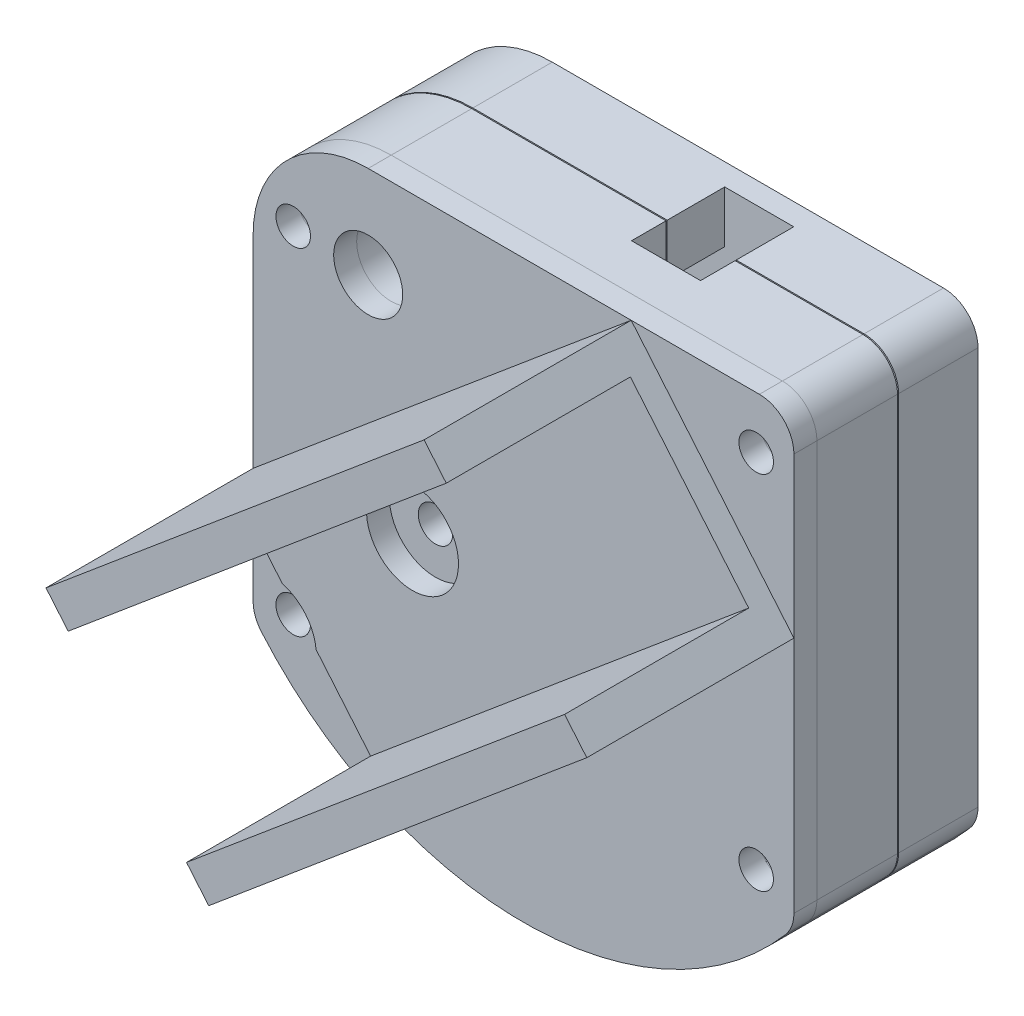
SolidWorks part; units mm, degrees
ref_plane "Front Plane" through (0, 0, 0) normal (0, 0, 1) x (1, 0, 0)
ref_plane "Top Plane" through (0, 0, 0) normal (0, 1, 0) x (1, 0, 0)
ref_plane "Right Plane" through (0, 0, 0) normal (1, 0, 0) x (0, 0, -1)
sketch "Sketch1" plane through (0, 0, 0) normal (0, 0, 1) x (1, 0, 0)
  line L0 (-11.1125, 0) -> (11.1125, 0) construction
  line L1 (17.1125, 10) -> (-29.8875, 10)
  line L2 (17.1125, 10) -> (17.1125, -40)
  line L3 (17.1125, -40) -> (-29.8875, -40)
  line L4 (-29.8875, 10) -> (-29.8875, -40)
  line L5 (11.1125, 0) -> (11.1125, -18) construction
  dimension "D1" = 10
  dimension "D2" = 47
  dimension "D3" = 6
  dimension "D4" = 50
extrude "Boss-Extrude1" add sketch "Sketch1" along normal blind 4 and the other way blind 10
sketch "Sketch2" plane through (0, -40, 0) normal (0, -1, 0) x (1, 0, 0)
  line L0 (-29.8875, -10) -> (-29.8875, 4) construction
  circle A0 centre (-19.8875, -3) radius 3.25
  point P4 (0, 0)
  point P5 (-29.8875, -3)
  dimension "D1" = 6.5
  dimension "D2" = 10
extrude "Cut-Extrude1" cut sketch "Sketch2" against normal blind 34
sketch "Sketch3" plane through (0, 0, 4) normal (0, 0, 1) x (1, 0, 0)
  line L0 (-29.8875, 10) -> (-29.8875, -40) construction
  line L1 (17.1125, -40) -> (17.1125, 10) construction
  line L5 (-29.8875, -40) -> (17.1125, -40) construction
  line L6 (-29.8875, -28.6481) -> (-29.8875, -40)
  line L7 (-29.8875, -40) -> (17.1125, -40)
  line L8 (17.1125, -40) -> (17.1125, -28.6481)
  arc A0 (-29.8875, -28.6481) -> (17.1125, -28.6481) centre (-6.3875, -10) ccw
  line M2 (17.1125, -40) -> (17.1125, 10)
  line M4 (-29.8875, 10) -> (-29.8875, -40)
  line M5 (-29.8875, -40) -> (17.1125, -40)
  dimension "D1" = 30
extrude "Cut-Extrude2" cut sketch "Sketch3" against normal blind 34 contours A0 M4 M5 | A0 L7 M2
fillet "Fillet6" radius 3 2 edges at (-29.8875, -28.6481, -3) (17.1125, -28.6481, -3)
sketch "Sketch5" plane through (0, 0, 0) normal (0, 1, 0) x (1, 0, 0)
  line L0 (-11.1125, 0) -> (11.1125, 0) construction
  line L1 (-42.8973, 0) -> (36.217, 0)
  line L2 (-42.8973, 0) -> (-42.8973, 0.1)
  line L3 (-42.8973, 0.1) -> (36.217, 0.1)
  line L4 (36.217, 0) -> (36.217, 0.1)
  dimension "D1" = 0.1
extrude "Cut-Extrude3" cut sketch "Sketch5" against normal through all both and the other way through all
sketch "Sketch6" plane through (0, 0, 0) normal (0, 0, -1) x (-1, 0, 0)
  line L0 (-9.75, -19.3625) -> (-9.75, -21.1375) construction
  line L1 (9.75, -21.1375) -> (9.75, -19.3625) construction
  line L2 (-11.1125, 0) -> (-11.1125, -18) construction
  line L4 (-11.6125, 10) -> (-11.6125, -18.3543)
  line L6 (11.6125, 10) -> (11.6125, -18.3543)
  line L7 (11.1125, -85.0724) -> (11.1125, -22.5) construction
  line L8 (29.8875, 10) -> (-17.1125, 10) construction
  line L9 (-11.6125, 10) -> (-17.1125, 10)
  line L10 (11.6125, -22.1457) -> (11.6125, -39.5415)
  line L11 (-11.6125, -22.1457) -> (-11.6125, -34)
  line L12 (-11.6125, 0.5) -> (-7.4, 0.5)
  line L13 (-3, 5.5) -> (-3, 10)
  line L14 (3, 10) -> (3, 5.5)
  line L15 (-17.1125, 10) -> (-17.1125, -27.5713)
  line L16 (18.6375, -37.385) -> (18.6375, -6)
  line L17 (18.6375, -6) -> (21.1375, -6)
  line L18 (21.1375, -6) -> (21.1375, -36.1235)
  line L19 (29.8875, -27.5713) -> (29.8875, 10)
  line L20 (29.8875, 10) -> (-17.1125, 10)
  line L21 (-17.1125, 10) -> (-17.1125, -27.5713)
  line L22 (18.6375, -37.385) -> (18.6375, -6)
  line L23 (18.6375, -6) -> (21.1375, -6)
  line L24 (21.1375, -6) -> (21.1375, -36.1235)
  line L25 (29.8875, -27.5713) -> (29.8875, 10)
  line L26 (29.8875, 10) -> (11.6125, 10)
  line L27 (3, 5.5) -> (7.4, 5.5)
  line L28 (3, 10) -> (11.6125, 10)
  line L29 (-11.6125, 10) -> (-3, 10)
  line L30 (-7.4, 0.5) -> (-7.4, 5.5)
  line L31 (-7.4, 5.5) -> (-3, 5.5)
  line L32 (7.4, 5.5) -> (7.4, 0.5)
  line L33 (7.4, 0.5) -> (11.6125, 0.5)
  line L34 (11.1125, 0) -> (-11.1125, 0) construction
  line L35 (-5, 2.5) -> (-5, -4.5) construction
  line L36 (5, -4.5) -> (5, 2.5) construction
  arc A0 (-11.6125, -22.1457) -> (-11.6125, -18.3543) centre (-12.25, -20.25) ccw
  arc A1 (11.6125, -18.3543) -> (11.6125, -22.1457) centre (12.25, -20.25) ccw
  arc A2 (-16.3903, -29.5236) -> (18.6375, -37.385) centre (6.3875, -10) ccw construction
  arc A3 (11.6125, -39.5415) -> (18.6375, -37.385) centre (6.3875, -10) ccw
  arc A5 (-16.3903, -29.5236) -> (18.6375, -37.385) centre (6.3875, -10) ccw
  arc A6 (21.1375, -36.1235) -> (29.1653, -29.5236) centre (6.3875, -10) ccw
  arc A7 (-16.3903, -29.5236) -> (-11.6125, -34) centre (6.3875, -10) ccw
  arc A8 (21.1375, -36.1235) -> (29.1653, -29.5236) centre (6.3875, -10) ccw
  arc A12 (-17.1125, -27.5713) -> (-16.3903, -29.5236) centre (-14.1125, -27.5713) ccw
  arc A13 (-17.1125, -27.5713) -> (-16.3903, -29.5236) centre (-14.1125, -27.5713) ccw
  arc A14 (29.1653, -29.5236) -> (29.8875, -27.5713) centre (26.8875, -27.5713) ccw
  arc A15 (29.1653, -29.5236) -> (29.8875, -27.5713) centre (26.8875, -27.5713) ccw
  point P11 (-9.75, -20.25)
  point P15 (9.75, -20.25)
  point P49 (0, 0)
  point P50 (0, 0)
  point P51 (0, 0)
  line M11 (-17.1125, 10) -> (-17.1125, -27.5713)
  arc M12 (-16.3903, -29.5236) -> (18.6375, -37.385) centre (6.3875, -10) ccw
  line M13 (18.6375, -37.385) -> (18.6375, -6)
  line M14 (18.6375, -6) -> (21.1375, -6)
  line M15 (21.1375, -6) -> (21.1375, -36.1235)
  arc M16 (21.1375, -36.1235) -> (29.1653, -29.5236) centre (6.3875, -10) ccw
  line M17 (29.8875, -27.5713) -> (29.8875, 10)
  line M18 (29.8875, 10) -> (-17.1125, 10)
  dimension "D1" = 4
  dimension "D2" = 4
  dimension "D3" = 2.5
  dimension "D4" = 2.5
  dimension "D5" = 0.5
  dimension "D6" = 0.5
  dimension "D8" = 0.5
  dimension "D9" = 2.4
  dimension "D10" = 5
  dimension "D11" = 2.4
  dimension "D12" = 6
  dimension "D7" = 0
extrude "Boss-Extrude2" add sketch "Sketch6" along normal blind 3 contours L30 L31 L13 L4 L12 M18 | L11 A0 L4 M18 M11 M12 | L6 A1 L10 M12 M13 M14 M15 M16 M17 M18 | L32 L33 L6 L14 L27 M18
sketch "Sketch7" plane through (0, -6, 0) normal (0, -1, 0) x (1, 0, 0)
  circle A0 centre (-19.8951, -2.9003) radius 3.35
extrude "Cut-Extrude4" cut sketch "Sketch7" along normal through all
sketch "Sketch8" plane through (0, 10, 0) normal (0, 1, 0) x (1, 0, 0)
  line L0 (3, 3) -> (17.1125, 3) construction
  line L1 (17.1125, 3.1) -> (-29.8875, 3.1)
  line L2 (17.1125, 3.1) -> (17.1125, 0.1)
  line L3 (17.1125, 0.1) -> (-29.8875, 0.1)
  line L4 (-29.8875, 3.1) -> (-29.8875, 0.1)
  line L5 (17.1125, 3) -> (17.1125, -4) construction
  line L6 (-29.8875, 3) -> (-29.8875, -4) construction
  line L7 (17.1125, 0.1) -> (-29.8875, 0.1) construction
  point P6 (17.1125, -2.831)
  point P9 (-29.8875, -2.831)
  point P12 (-29.8875, 0)
  point P13 (17.1125, 0)
  dimension "D1" = 0.1
extrude "Cut-Extrude5" cut sketch "Sketch8" against normal through all both and the other way through all
chamfer "Chamfer1" distance 4 angle 70 1 edges at (-19.8875, -6, -3.1)
sketch "Sketch9" plane through (0, -6, 0) normal (0, -1, 0) x (1, 0, 0)
  line L1 (-23.2437, -3) -> (-16.5466, -3)
  line L3 (-23.2437, -3) -> (-16.5466, -3)
  arc A1 (-16.5466, -3) -> (-23.2437, -3) centre (-19.8951, -2.9003) ccw
  arc A3 (-16.5466, -3) -> (-23.2437, -3) centre (-19.8951, -2.9003) ccw
  dimension "D1" = 0
extrude "Cut-Extrude6" cut sketch "Sketch9" against normal up to vertex (11.2647 mm away)
sketch "Sketch11" plane through (0, 0.5, 0) normal (0, -1, 0) x (1, 0, 0)
  line L0 (16.3903, -3.1) -> (-16.639, -3.1) construction
  line L1 (-10.6125, -3.1) -> (10.6125, -3.1)
  line L2 (-10.6125, -3.1) -> (-10.6125, -1.2)
  line L3 (-10.6125, -1.2) -> (10.6125, -1.2)
  line L4 (10.6125, -3.1) -> (10.6125, -1.2)
  line L5 (11.6125, -3) -> (11.6125, 0) construction
  line L6 (-11.6125, -3) -> (-11.6125, 0) construction
  line L7 (0, -0.9) -> (-10.1826, -0.9) construction
  dimension "D1" = 1
  dimension "D2" = 1
  dimension "D3" = 0.3
extrude "Boss-Extrude3" add sketch "Sketch11" along normal up to surface (15.201 mm away) from offset 25
sketch "Sketch12" plane through (0, 0, -3.1) normal (0, 0, 1) x (1, 0, 0)
  line L0 (-11.6125, -8) -> (11.6125, -8)
  line L1 (-3, 10) -> (3, 10)
  line L8 (7.4, 5.5) -> (7.4, 0.5)
  line L9 (3, 5.5) -> (7.4, 5.5)
  line L10 (3, 10) -> (3, 5.5)
  line L11 (17.1125, 10) -> (3, 10)
  line L12 (17.1125, -27.5713) -> (17.1125, 10)
  line L13 (11.6125, -22.1457) -> (11.6125, -34)
  line L14 (11.6125, 0.5) -> (11.6125, -18.3543)
  line L15 (7.4, 0.5) -> (11.6125, 0.5)
  line L16 (7.4, 5.5) -> (7.4, 0.5)
  line L17 (3, 5.5) -> (7.4, 5.5)
  line L18 (3, 10) -> (3, 5.5)
  line L19 (17.1125, 10) -> (3, 10)
  line L21 (11.6125, -22.1457) -> (11.6125, -34)
  line L22 (11.6125, 0.5) -> (11.6125, -18.3543)
  line L23 (7.4, 0.5) -> (11.6125, 0.5)
  line L27 (-23.2437, 4.9899) -> (-16.5466, 4.9899)
  line L28 (-23.2437, -34.8167) -> (-23.2437, 4.9899)
  line L29 (-29.8875, 10) -> (-29.8875, -27.5713)
  line L30 (-3, 10) -> (-29.8875, 10)
  line L31 (-3, 5.5) -> (-3, 10)
  line L32 (-7.4, 5.5) -> (-3, 5.5)
  line L33 (-7.4, 0.5) -> (-7.4, 5.5)
  line L34 (-11.6125, 0.5) -> (-7.4, 0.5)
  line L35 (-11.6125, -18.3543) -> (-11.6125, 0.5)
  line L36 (-11.6125, -39.5415) -> (-11.6125, -22.1457)
  line L37 (-16.5466, 4.9899) -> (-16.5466, -38.2275)
  line L42 (-3, 5.5) -> (-3, 10)
  line L43 (-7.4, 5.5) -> (-3, 5.5)
  line L44 (-7.4, 0.5) -> (-7.4, 5.5)
  line L45 (-11.6125, 0.5) -> (-7.4, 0.5)
  line L46 (-11.6125, -18.3543) -> (-11.6125, 0.5)
  line L47 (-11.6125, -39.5415) -> (-11.6125, -22.1457)
  line L51 (-23.2437, 4.9899) -> (-16.5466, 4.9899)
  arc A2 (11.6125, -34) -> (16.3903, -29.5236) centre (-6.3875, -10) ccw
  arc A3 (11.6125, -18.3543) -> (11.6125, -22.1457) centre (12.25, -20.25) ccw
  arc A5 (11.6125, -18.3543) -> (11.6125, -22.1457) centre (12.25, -20.25) ccw
  arc A7 (-29.1653, -29.5236) -> (-23.2437, -34.8167) centre (-6.3875, -10) ccw
  arc A8 (-11.6125, -22.1457) -> (-11.6125, -18.3543) centre (-12.25, -20.25) ccw
  arc A9 (-16.5466, -38.2275) -> (-11.6125, -39.5415) centre (-6.3875, -10) ccw
  arc A11 (-11.6125, -22.1457) -> (-11.6125, -18.3543) centre (-12.25, -20.25) ccw
  arc A13 (16.3903, -29.5236) -> (17.1125, -27.5713) centre (14.1125, -27.5713) ccw
  arc A14 (16.3903, -29.5236) -> (17.1125, -27.5713) centre (14.1125, -27.5713) ccw
  arc A16 (-29.8875, -27.5713) -> (-29.1653, -29.5236) centre (-26.8875, -27.5713) ccw
  arc A17 (-29.8875, -27.5713) -> (-29.1653, -29.5236) centre (-26.8875, -27.5713) ccw
  line M32 (17.1125, 10) -> (-29.8875, 10)
  dimension "D3" = 18
  dimension "D1" = 0
  dimension "D2" = 0
extrude "Cut-Extrude8" cut sketch "Sketch12" against normal blind 5 contours L46 L0 L22 L23 L16 L17 L18 L42 L43 L44 L45 M32
sketch "Sketch13" plane through (0, 0, 4) normal (0, 0, 1) x (1, 0, 0)
  line L0 (17.1125, -6.853) -> (2.9712, 10)
  line L1 (17.1125, -6.853) -> (-15.7462, -34.4247)
  line L2 (2.9712, 10) -> (-29.8875, -17.5717)
  line L3 (-15.7462, -34.4247) -> (-29.8875, -17.5717)
  line L4 (17.1125, -27.5713) -> (17.1125, 10) construction
  line L5 (17.1125, 10) -> (-29.8875, 10) construction
  line L6 (-29.8875, 10) -> (-29.8875, -27.5713) construction
  point P6 (0, 0)
  point P7 (0, 0)
  point P8 (-41.2551, 21.0545)
  point P11 (0, 0)
  dimension "D1" = 130
  dimension "D2" = 22
extrude "Boss-Extrude4" add sketch "Sketch13" along normal blind 20 separate body
fillet "Fillet1" radius 10 1 edges at (-29.8875, 10, 0.5)
sketch "Sketch15" plane through (0, 0, 4) normal (0, 0, 1) x (1, 0, 0)
  line L14 (17.1125, 10) -> (-19.8875, 10)
  line L15 (-29.8875, 0) -> (-29.8875, -27.5713)
  line L16 (17.1125, -27.5713) -> (17.1125, 10)
  line L17 (17.1125, 10) -> (-19.8875, 10)
  line L18 (-29.8875, 0) -> (-29.8875, -27.5713)
  line L19 (17.1125, -27.5713) -> (17.1125, 10)
  arc A8 (-19.8875, 10) -> (-29.8875, 0) centre (-19.8875, 0) ccw
  arc A9 (-29.1653, -29.5236) -> (16.3903, -29.5236) centre (-6.3875, -10) ccw
  arc A10 (-19.8875, 10) -> (-29.8875, 0) centre (-19.8875, 0) ccw
  arc A11 (-29.1653, -29.5236) -> (16.3903, -29.5236) centre (-6.3875, -10) ccw
  arc A14 (-29.8875, -27.5713) -> (-29.1653, -29.5236) centre (-26.8875, -27.5713) ccw
  arc A15 (-29.8875, -27.5713) -> (-29.1653, -29.5236) centre (-26.8875, -27.5713) ccw
  arc A16 (16.3903, -29.5236) -> (17.1125, -27.5713) centre (14.1125, -27.5713) ccw
  arc A17 (16.3903, -29.5236) -> (17.1125, -27.5713) centre (14.1125, -27.5713) ccw
  dimension "D1" = 0
extrude "Boss-Extrude5" add sketch "Sketch15" along normal blind 2
sketch "Sketch16" plane through (-26.1911, -21.9769, 0) normal (-0.766, -0.6428, 0) x (0, 0, 1)
  line L0 (24, 5.7506) -> (24, -16.2494) construction
  line L1 (24, 2.7506) -> (8, 2.7506)
  line L2 (24, 2.7506) -> (24, -13.2494)
  line L3 (24, -13.2494) -> (8, -13.2494)
  line L4 (8, 2.7506) -> (8, -13.2494)
  line L6 (6, 5.7506) -> (6, -16.2494) construction
  point P6 (8, 4.8465)
  point P11 (6, -5.2494)
  point P12 (8, -5.2494)
  dimension "D1" = 16
  dimension "D2" = 16
extrude "Cut-Extrude9" cut sketch "Sketch16" against normal through all
sketch "Sketch17" plane through (0, 0, 6) normal (0, 0, 1) x (1, 0, 0)
  line L21 (-3, 5.5) -> (-3, 10)
  line L22 (-3, 10) -> (-29.8875, 10)
  line L23 (-29.8875, 10) -> (-29.8875, -27.5713)
  line L24 (-23.136, -34.8895) -> (-23.136, 4.9899)
  line L25 (-23.136, 4.9899) -> (-16.639, 4.9899)
  line L26 (-16.639, 4.9899) -> (-16.639, -38.1941)
  line L27 (-10.6125, -39.701) -> (-10.6125, -24.5)
  line L28 (-10.6125, -24.5) -> (10.6125, -24.5)
  line L29 (10.6125, -24.5) -> (10.6125, -34.7184)
  line L30 (17.1125, -27.5713) -> (17.1125, 10)
  line L31 (17.1125, 10) -> (3, 10)
  line L32 (3, 10) -> (3, 5.5)
  line L33 (3, 5.5) -> (7.4, 5.5)
  line L34 (7.4, 5.5) -> (7.4, 0.5)
  line L35 (7.4, 0.5) -> (11.6125, 0.5)
  line L36 (11.6125, 0.5) -> (11.6125, -8)
  line L37 (11.6125, -8) -> (-11.6125, -8)
  line L38 (-11.6125, -8) -> (-11.6125, 0.5)
  line L39 (-11.6125, 0.5) -> (-7.4, 0.5)
  line L40 (-7.4, 0.5) -> (-7.4, 5.5)
  line L41 (-7.4, 5.5) -> (-3, 5.5)
  line L42 (-3, 5.5) -> (-3, 10) construction
  line L43 (-3, 10) -> (-29.8875, 10) construction
  line L44 (-29.8875, 10) -> (-29.8875, -27.5713) construction
  line L45 (-23.136, -34.8895) -> (-23.136, 4.9899) construction
  line L47 (-16.639, 4.9899) -> (-16.639, -38.1941) construction
  line L48 (-10.6125, -39.701) -> (-10.6125, -24.5) construction
  line L49 (-10.6125, -24.5) -> (10.6125, -24.5) construction
  line L50 (10.6125, -24.5) -> (10.6125, -34.7184) construction
  line L51 (17.1125, -27.5713) -> (17.1125, 10) construction
  line L52 (17.1125, 10) -> (3, 10) construction
  line L53 (3, 10) -> (3, 5.5) construction
  line L54 (3, 5.5) -> (7.4, 5.5) construction
  line L55 (7.4, 5.5) -> (7.4, 0.5) construction
  line L56 (7.4, 0.5) -> (11.6125, 0.5) construction
  line L57 (11.6125, 0.5) -> (11.6125, -8) construction
  line L58 (11.6125, -8) -> (-11.6125, -8) construction
  line L59 (-11.6125, -8) -> (-11.6125, 0.5) construction
  line L60 (-11.6125, 0.5) -> (-7.4, 0.5) construction
  line L61 (-7.4, 0.5) -> (-7.4, 5.5) construction
  line L62 (-7.4, 5.5) -> (-3, 5.5) construction
  line L64 (-23.136, 4.9899) -> (-16.639, 4.9899)
  circle A0 centre (13.836, -25.8976) radius 1.5
  circle A1 centre (-14.0368, -13.8474) radius 1.5
  circle A2 centre (-26.4014, 2.3943) radius 1.5
  arc A3 (-29.1653, -29.5236) -> (-23.136, -34.8895) centre (-6.3875, -10) ccw
  arc A4 (-16.639, -38.1941) -> (-10.6125, -39.701) centre (-6.3875, -10) ccw
  arc A5 (10.6125, -34.7184) -> (16.3903, -29.5236) centre (-6.3875, -10) ccw
  arc A6 (-29.1653, -29.5236) -> (-23.136, -34.8895) centre (-6.3875, -10) ccw construction
  arc A7 (-16.639, -38.1941) -> (-10.6125, -39.701) centre (-6.3875, -10) ccw construction
  arc A8 (10.6125, -34.7184) -> (16.3903, -29.5236) centre (-6.3875, -10) ccw construction
  circle A9 centre (13.836, 5.5) radius 1.5
  circle A10 centre (-26.4014, -26.8407) radius 1.5
  arc A16 (-29.8875, -27.5713) -> (-29.1653, -29.5236) centre (-26.8875, -27.5713) ccw
  arc A17 (-29.8875, -27.5713) -> (-29.1653, -29.5236) centre (-26.8875, -27.5713) ccw
  arc A18 (16.3903, -29.5236) -> (17.1125, -27.5713) centre (14.1125, -27.5713) ccw
  arc A19 (16.3903, -29.5236) -> (17.1125, -27.5713) centre (14.1125, -27.5713) ccw
  point P18 (-26.4014, 2.3943)
  point P20 (-14.0368, -13.8474)
  point P29 (13.836, 5.5)
  point P31 (-26.4014, -26.8407)
  dimension "D2" = 3
  dimension "D3" = 3
  dimension "D4" = 3
  dimension "D1" = 0
extrude "Cut-Extrude10" cut sketch "Sketch17" against normal through all contours A10 | A2 | A1 | A0 | A9
sketch "Sketch10" plane through (0, 0, -3.1) normal (0, 0, 1) x (1, 0, 0)
  line L3 (-23.2437, 4.9899) -> (-16.5466, 4.9899) construction
  circle A0 centre (-19.8875, 1.9899) radius 3
  point P2 (0, 0)
  point P5 (0, 0)
  point P8 (0, 0)
  dimension "D1" = 6
extrude "Cut-Extrude7" cut sketch "Sketch10" along normal blind 10
fillet "Fillet2" radius 10 1 edges at (-29.8875, 10, -6.55)
fillet "Fillet3" radius 3 1 edges at (17.1125, 10, -6.55)
fillet "Fillet4" radius 3 1 edges at (17.1125, 10, 0.5)
fillet "Fillet5" radius 3 1 edges at (17.1125, 10, 5)
sketch "Sketch18" plane through (0, 0, 8) normal (0, 0, 1) x (1, 0, 0)
  circle A0 centre (-14.0368, -13.8474) radius 4
  circle A1 centre (-26.4014, -26.8407) radius 4
  point P0 (-14.0368, -13.8474)
  dimension "D1" = 8
  dimension "D2" = 8
extrude "Cut-Extrude11" cut sketch "Sketch18" against normal blind 2
